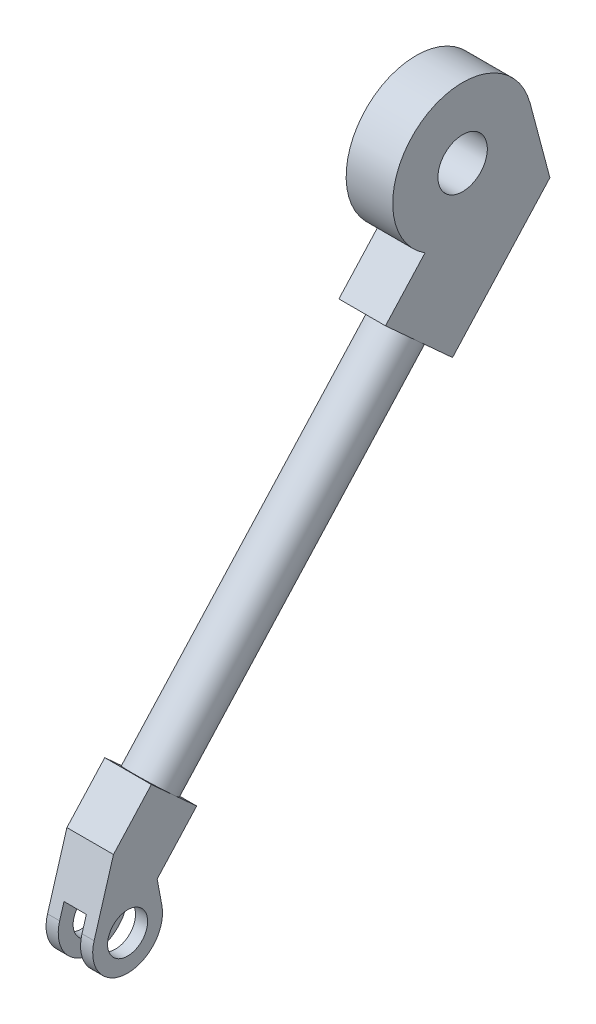
SolidWorks part; units mm, degrees
ref_plane "Front Plane" through (0, 0, 0) normal (0, 0, 1) x (1, 0, 0)
ref_plane "Top Plane" through (0, 0, 0) normal (0, 1, 0) x (1, 0, 0)
ref_plane "Right Plane" through (0, 0, 0) normal (1, 0, 0) x (0, 0, -1)
sketch "Sketch2" plane through (18.5048, 0, 0) normal (-1, 0, 0) x (0, 0, 1)
  line L0 (8.0962, 116.6813) -> (-0.3543, 100.7882) construction
  line L1 (8.0962, 116.6813) -> (8.0962, 99.1413) construction
  circle A0 centre (-0.3543, 100.7882) radius 7.5
  arc A1 (3.7661, 122.805) -> (12.4263, 122.805) centre (8.0962, 116.6813) ccw construction
  circle A2 centre (-0.3543, 100.7882) radius 2.65
  circle A3 centre (8.0962, 116.6813) radius 2.65 construction
  dimension "D1" = 28
  dimension "D2" = 18
extrude "Boss-Extrude1" add sketch "Sketch2" against normal up to surface (5 mm away)
sketch "Sketch3" plane through (18.5048, 0, 0) normal (-1, 0, 0) x (0, 0, 1)
  line L0 (32.9344, 59.5386) -> (1.9171, 93.6404) construction
  line L1 (32.9344, 59.5386) -> (37.0976, 54.9613) construction
  line L2 (28.4958, 55.5014) -> (-9.1504, 96.8914) construction
  line L3 (28.4958, 55.5014) -> (32.9344, 59.5386) construction
  line L4 (-9.1504, 96.8914) -> (-7.6026, 102.7148)
  line L5 (0.9366, 94.5751) -> (-7.6026, 102.7148)
  line L6 (3.6819, 94.4669) -> (7.9228, 89.8042)
  line L7 (7.9228, 89.8042) -> (0.7298, 83.2619)
  line L8 (0.7298, 83.2619) -> (-9.7195, 94.7504)
  line L9 (-9.7195, 94.7504) -> (-9.1504, 96.8914)
  line L10 (30.7151, 57.52) -> (4.3263, 86.5331) construction
  line L11 (3.6819, 94.4669) -> (0.9366, 94.5751)
  circle A0 centre (-0.3543, 100.7882) radius 7.5 construction
  dimension "D1" = 6
extrude "Boss-Extrude2" add sketch "Sketch3" against normal up to surface (5 mm away) up to face at (23.5048, 100.7882, 7.1457)
sketch "Sketch4" plane through (0, 45.2028, -41.1141) normal (0, -0.7398, 0.6729) x (1, 0, 0)
  line L0 (21.0048, 61.4249) -> (21.0048, 66.2866) construction
  line L1 (23.5048, 66.2866) -> (18.5048, 66.2866) construction
  line L2 (21.0048, 61.4249) -> (23.5048, 61.4249) construction
  line L3 (23.5048, 66.2866) -> (23.5048, 56.5633) construction
  circle A0 centre (21.0048, 61.4249) radius 2.5
extrude "Boss-Extrude3" add sketch "Sketch4" along normal blind 45
sketch "Sketch5" plane through (18.5048, 0, 0) normal (-1, 0, 0) x (0, 0, 1)
  line L0 (39.19, 48.2904) -> (37.113, 55.2684)
  line L1 (37.113, 55.2684) -> (33.0492, 59.7363)
  line L2 (33.0492, 59.7363) -> (28.1848, 55.3119)
  line L3 (28.1848, 55.3119) -> (32.4238, 50.6514)
  line L4 (32.4238, 50.6514) -> (31.9126, 47.9078)
  line L5 (32.7555, 51.5612) -> (36.4543, 54.9255) construction
  line L6 (36.4543, 54.9255) -> (6.1757, 88.2152) construction
  arc A0 (31.9126, 47.9078) -> (39.19, 48.2904) centre (35.5974, 47.2211) ccw
extrude "Boss-Extrude4" add sketch "Sketch5" against normal up to surface (5 mm away) up to face at (23.5048, 93.2973, 0.8951)
sketch "Sketch6" plane through (23.5048, 0, 0) normal (1, 0, 0) x (0, 0, -1)
  circle A0 centre (-35.5974, 47.2211) radius 2.15
  dimension "D1" = 4.3
extrude "Cut-Extrude1" cut sketch "Sketch6" against normal through all both and the other way through all
ref_plane "Plane1" through (21.0048, 0, 0) normal (1, 0, 0) x (0, 0, -1)
sketch "Sketch7" plane through (21.0048, 0, 0) normal (1, 0, 0) x (0, 0, -1)
  circle A0 centre (-35.5974, 47.2211) radius 4.089
extrude "Cut-Extrude2" cut sketch "Sketch7" against normal mid plane 2.4
move or copy body "Body-Move/Copy1" bodies to move or copy 106 copy no translate (-21, -100.79, 0.35)
ref_axis "Axis1" through (-4.568, -53.5689, 35.9474) along (1, 0, 0)
ref_axis "Axis2" through (3.7042, -0.0018, -0.0043) along (-1, 0, 0)
